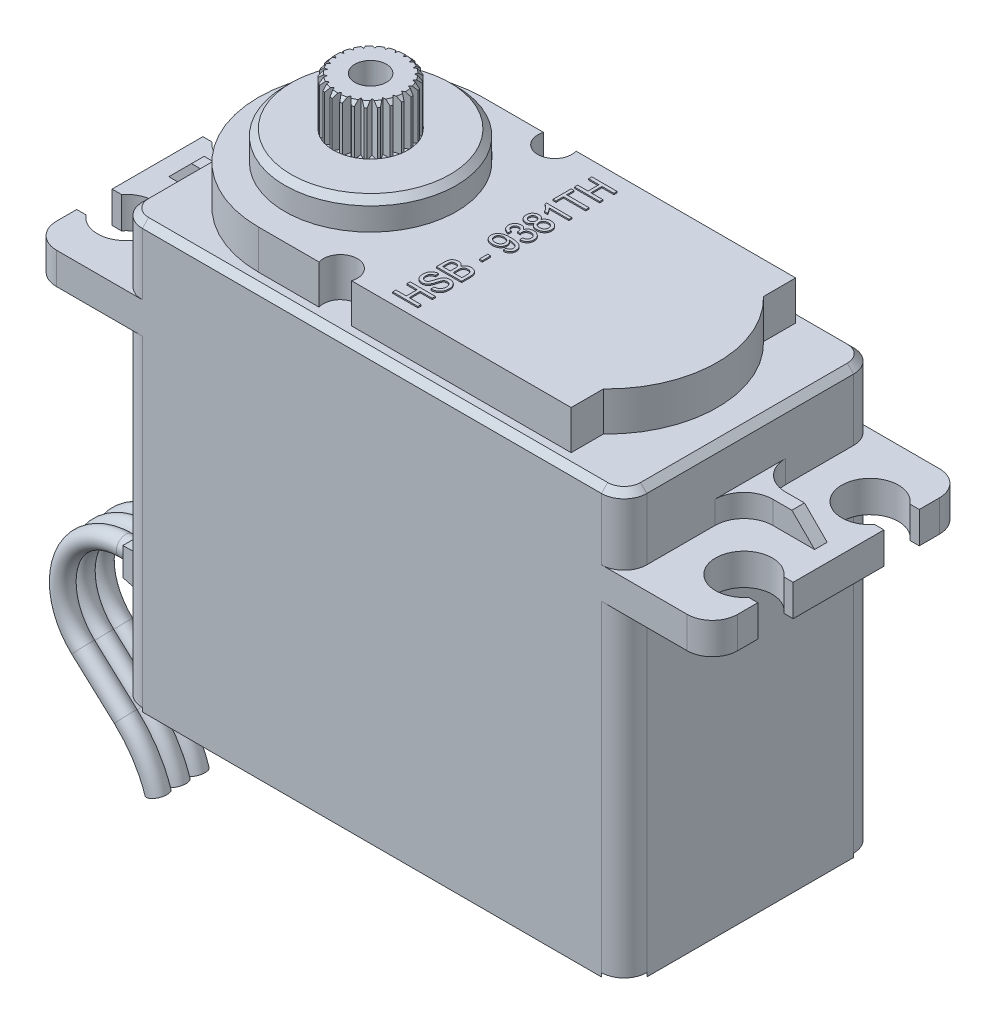
SolidWorks part; units mm, degrees
ref_plane "Ebene vorne" through (0, 0, 0) normal (0, 0, 1) x (1, 0, 0)
ref_plane "Ebene oben" through (0, 0, 0) normal (0, 1, 0) x (1, 0, 0)
ref_plane "Ebene rechts" through (0, 0, 0) normal (1, 0, 0) x (0, 0, -1)
sketch "Skizze1" plane through (0, 0, 0) normal (0, 0, 1) x (1, 0, 0)
  line L1 (-27, 27) -> (-20, 27)
  line L2 (-20, 27) -> (-20, 0)
  line L7 (-20, 0) -> (20, 0)
  line L8 (20, 0) -> (20, 27)
  line L9 (20, 27) -> (27, 27)
  line L10 (27, 27) -> (27, 29.5)
  line L11 (27, 29.5) -> (20, 29.5)
  line L12 (20, 29.5) -> (20, 34.9)
  line L14 (20, 34.9) -> (-20, 34.9)
  line L20 (-20, 34.9) -> (-20, 29.5)
  line L21 (-20, 29.5) -> (-27, 29.5)
  line L22 (-27, 29.5) -> (-27, 27)
  dimension "D1" = 40
  dimension "D2" = 27
  dimension "D6" = 54
  dimension "D7" = 2.5
  dimension "D11" = 5.4
extrude "Aufsatz-Linear austragen1" add sketch "Skizze1" along normal mid plane 20
sketch "Skizze2" plane through (0, 29.5, 0) normal (0, 1, 0) x (1, 0, 0)
  line L1 (24.5, -5) -> (-24.5, -5) construction
  line L2 (24.5, -5) -> (24.5, 5) construction
  line L3 (24.5, 5) -> (-24.5, 5) construction
  line L4 (-24.5, -5) -> (-24.5, 5) construction
  line L5 (24.5, -5) -> (-24.5, 5) construction
  line L6 (24.5, 5) -> (-24.5, -5) construction
  circle A0 centre (-24.5, 5) radius 2.25
  circle A1 centre (24.5, 5) radius 2.25
  circle A2 centre (24.5, -5) radius 2.25
  circle A3 centre (-24.5, -5) radius 2.25
  point P0 (0, 0)
  dimension "D1" = 4.5
  dimension "D2" = 10
  dimension "D3" = 49
extrude "Schnitt-Linear austragen1" cut sketch "Skizze2" against normal through all
sketch "Skizze6" plane through (0, 34.9, 0) normal (0, 1, 0) x (1, 0, 0)
  line L0 (-10.1, 8.9) -> (14.7, 8.9)
  line L1 (14.7, 8.9) -> (14.7, 6.35)
  line L2 (14.7, -6.35) -> (14.7, -8.9)
  line L3 (14.7, -8.9) -> (-10.1, -8.9)
  line L4 (-10.1, 0) -> (20, 0) construction
  line L5 (20, -10) -> (20, 10) construction
  line L6 (-20, -10) -> (-20, 10) construction
  line L8 (20, -10) -> (20, 10) construction
  arc A0 (-10.1, -8.9) -> (-10.1, 8.9) centre (-10.1, 0) cw
  arc A1 (14.7, 6.35) -> (14.7, -6.35) centre (8.5829, 0) cw
  circle A2 centre (24.5, 5) radius 2.25 construction
  point P13 (17.4, 0)
  point P17 (-19, 0)
  dimension "D1" = 17.8
  dimension "D2" = 34.7
  dimension "D3" = 12.7
  dimension "D4" = 2.6
  dimension "D5" = 34.6
extrude "Aufsatz-Linear austragen3" add sketch "Skizze6" along normal blind 3.1
sketch "Skizze7" plane through (0, 38, 0) normal (0, 1, 0) x (1, 0, 0)
  circle A0 centre (-10.1, 0) radius 6.8
  arc A1 (-10.1, 8.9) -> (-10.1, -8.9) centre (-10.1, 0) ccw construction
  dimension "D1" = 13.6
extrude "Aufsatz-Linear austragen4" add sketch "Skizze7" along normal blind 2.3
sketch "Skizze3" plane through (0, 40.3, 0) normal (0, 1, 0) x (1, 0, 0)
  circle A0 centre (-10.1, 0) radius 2.95
  circle A1 centre (-10.1, 0) radius 6.8 construction
  dimension "D1" = 5.9
extrude "Aufsatz-Linear austragen2" add sketch "Skizze3" along normal blind 3.8
fillet "Verrundung1" radius 2 4 edges at (27, 28.25, -10) (27, 28.25, 10) (-27, 28.25, -10) (-27, 28.25, 10)
sketch "Skizze4" plane through (0, 29.5, 0) normal (0, 1, 0) x (1, 0, 0)
  line L1 (-26.75, -5) -> (26.75, -5) construction
  line L2 (-25.75, 3.6) -> (-27.75, 3.6)
  line L3 (-25.75, 3.6) -> (-25.75, 6.4)
  line L4 (-25.75, 6.4) -> (-27.75, 6.4)
  line L5 (-27.75, 3.6) -> (-27.75, 6.4)
  line L6 (-25.75, 3.6) -> (-27.75, 6.4) construction
  line L7 (-25.75, 6.4) -> (-27.75, 3.6) construction
  line L8 (-25.75, -6.4) -> (-27.75, -6.4)
  line L9 (-25.75, -6.4) -> (-25.75, -3.6)
  line L10 (-25.75, -3.6) -> (-27.75, -3.6)
  line L11 (-27.75, -6.4) -> (-27.75, -3.6)
  line L12 (-25.75, -6.4) -> (-27.75, -3.6) construction
  line L13 (-25.75, -3.6) -> (-27.75, -6.4) construction
  line L14 (25.75, 6.4) -> (27.75, 6.4)
  line L15 (25.75, 6.4) -> (25.75, 3.6)
  line L16 (25.75, 3.6) -> (27.75, 3.6)
  line L17 (27.75, 6.4) -> (27.75, 3.6)
  line L18 (25.75, 6.4) -> (27.75, 3.6) construction
  line L19 (25.75, 3.6) -> (27.75, 6.4) construction
  line L20 (25.75, -3.6) -> (27.75, -3.6)
  line L21 (25.75, -3.6) -> (25.75, -6.4)
  line L22 (25.75, -6.4) -> (27.75, -6.4)
  line L23 (27.75, -3.6) -> (27.75, -6.4)
  line L24 (25.75, -3.6) -> (27.75, -6.4) construction
  line L25 (25.75, -6.4) -> (27.75, -3.6) construction
  line L26 (26.75, -5) -> (26.75, 5) construction
  line L27 (26.75, 5) -> (-26.75, 5) construction
  line L28 (-26.75, 5) -> (-26.75, -5) construction
  line L29 (-24.5, 5) -> (-26.75, 5) construction
  circle A0 centre (-24.5, 5) radius 2.25 construction
  circle A1 centre (-24.5, -5) radius 2.25 construction
  circle A2 centre (24.5, 5) radius 2.25 construction
  circle A3 centre (24.5, -5) radius 2.25 construction
  point P0 (-26.75, -5)
  point P2 (-26.75, 5)
  point P14 (26.75, 5)
  point P21 (26.75, -5)
  dimension "D1" = 2.8
  dimension "D2" = 2
extrude "Schnitt-Linear austragen2" cut sketch "Skizze4" against normal through all
chamfer "Fase1" distance 0.3 angle 45 1 edges at (-10.1, 44.1, 2.95)
sketch "Skizze5" plane through (0, 44.1, 0) normal (0, 1, 0) x (1, 0, 0)
  line L0 (-7.15, 0) -> (-10.1, 0) construction
  line L1 (-7.15, 0.2887) -> (-7.15, -0.2887)
  line L2 (-7.15, -0.2887) -> (-7.65, 0)
  line L3 (-7.65, 0) -> (-7.15, 0.2887)
  circle A0 centre (-10.1, 0) radius 2.95 construction
  circle A1 centre (-10.1, 0) radius 2.95 construction
  dimension "D1" = 0.5
extrude "Schnitt-Linear austragen3" cut sketch "Skizze5" against normal blind 3.9
pattern_circular "Kreismuster1" count 25 over 360 about axis through (-10.1, 44.1, 0) along (0, -1, 0) of "Schnitt-Linear austragen3" reverse direction yes
fillet "Verrundung2" radius 1.8 8 edges at (-20, 32.2, 10) (-20, 13.5, 10) (-20, 32.2, -10) (-20, 13.5, -10) (20, 13.5, 10) (20, 32.2, 10) (20, 32.2, -10) (20, 13.5, -10)
chamfer "Fase2" distance 1.2 angle 45 8 edges at (0, 0, 10) (-19.4728, 0, 9.4728) (19.4728, 0, 9.4728) (-20, 0, 0) (20, 0, 0) (-19.4728, 0, -9.4728) (19.4728, 0, -9.4728) (0, 0, -10)
hole_wizard "M3 Gewindebohrung1" positions "Skizze8" profile "Skizze9" tap size "M3" standard "DIN"
sketch "Skizze8" plane through (0, 44.1, 0) normal (0, 1, 0) x (1, 0, 0)
  point P0 (-10.1, 0)
sketch "Skizze9" plane through (-10.1, 44.1, 0) normal (1, 0, 0) x (0, 0, 1)
  line L0 (0, 0) -> (0, 9.2511)
  line L1 (0, 9.2511) -> (1.25, 8.5)
  line L2 (1.25, 8.5) -> (1.25, 0)
  line L5 (1.25, 0) -> (0, 0)
  line L10 (0, 9.2511) -> (-1.25, 8.5) construction
  line L11 (0, -6.35) -> (0, 107.95) construction
  dimension "Bohrerdurchmesser" = 2.5
  dimension "Bohrungstiefe" = 8.5
  dimension "Spitzenwinkel" = 118
cosmetic thread "Bohrungsgewinde1" parameters "D1"=6, "D2"=3
chamfer "Fase3" distance 0.5 angle 45 9 edges at (-10.1, 40.3, 6.8) (0, 34.9, -10) (19.4728, 34.9, -9.4728) (-19.4728, 34.9, -9.4728) (20, 34.9, 0) (-20, 34.9, 0) (19.4728, 34.9, 9.4728) (-19.4728, 34.9, 9.4728) (0, 34.9, 10)
sketch "Skizze10" plane through (0, 0, 0) normal (0, -1, 0) x (1, 0, 0)
  line L0 (-18.2, 10) -> (18.2, 10) construction
  line L1 (-20, 8.2) -> (-20, -8.2) construction
  line L3 (18.2, -8.2) -> (-18.2, -8.2) construction
  line L4 (18.2, -8.2) -> (18.2, 8.2) construction
  line L5 (18.2, 8.2) -> (-18.2, 8.2) construction
  line L6 (-18.2, -8.2) -> (-18.2, 8.2) construction
  line L7 (18.2, -8.2) -> (-18.2, 8.2) construction
  line L8 (18.2, 8.2) -> (-18.2, -8.2) construction
  circle A0 centre (-18.2, 8.2) radius 1.8
  circle A1 centre (18.2, 8.2) radius 1.8
  circle A2 centre (18.2, -8.2) radius 1.8
  circle A3 centre (-18.2, -8.2) radius 1.8
  point P12 (0, 0)
  dimension "D1" = 3.6
extrude "Schnitt-Linear austragen4" cut sketch "Skizze10" against normal blind 1.5 contours A3 | A0 | A1 | A2
sketch "Skizze11" plane through (0, 38, 0) normal (0, 1, 0) x (1, 0, 0)
  line L0 (-4, 8.5) -> (-4, -8.5) construction
  line L1 (-4, 0) -> (0, 0) construction
  line L2 (-20, -8.2) -> (-20, 8.2) construction
  circle A0 centre (-4, 8.5) radius 1.35
  circle A1 centre (-4, -8.5) radius 1.35
  dimension "D1" = 17
  dimension "D2" = 2.7
  dimension "D3" = 16
extrude "Schnitt-Linear austragen5" cut sketch "Skizze11" against normal up to surface (3.1 mm away) up to face at (0, 34.9, 0)
sketch "Skizze12" plane through (-20, 0, 0) normal (-1, 0, 0) x (0, 0, 1)
  line L0 (6.5029, 0) -> (-6.5029, 0) construction
  line L1 (3.5, 1.5) -> (-3.5, 1.5)
  line L2 (3.5, 1.5) -> (3.5, 5.5)
  line L3 (3.5, 5.5) -> (-3.5, 5.5)
  line L4 (-3.5, 1.5) -> (-3.5, 5.5)
  line L5 (3.5, 1.5) -> (-3.5, 5.5) construction
  line L6 (3.5, 5.5) -> (-3.5, 1.5) construction
  line L7 (0, 0) -> (0, 3.5) construction
  point P0 (0, 3.5)
  dimension "D1" = 4
  dimension "D2" = 7
  dimension "D3" = 3.5
ref_plane "Ebene1" through (-27, 0, 0) normal (-1, 0, 0) x (0, 0, 1)
sketch "Skizze13" plane through (-27, 0, 0) normal (-1, 0, 0) x (0, 0, 1)
  line L1 (2.75, 2.4) -> (-2.75, 2.4)
  line L2 (2.75, 2.4) -> (2.75, 4.6)
  line L3 (2.75, 4.6) -> (-2.75, 4.6)
  line L4 (-2.75, 2.4) -> (-2.75, 4.6)
  line L5 (2.75, 2.4) -> (-2.75, 4.6) construction
  line L6 (2.75, 4.6) -> (-2.75, 2.4) construction
  point P0 (0, 3.5)
  dimension "D1" = 2.2
  dimension "D2" = 5.5
loft "Ausformung1" add profiles "Skizze13", "Skizze12" connector at (-27, 4.6, -2.75) connector at (-20, 5.5, -3.5)
sketch "Skizze15" plane through (-27, 0, 0) normal (-1, 0, 0) x (0, 0, 1)
  line L0 (-1.51, 3.5) -> (0, 3.5) construction
  line L1 (0, 3.5) -> (1.51, 3.5) construction
  circle A0 centre (0, 3.5) radius 0.75
  circle A1 centre (-1.51, 3.5) radius 0.75
  circle A2 centre (1.51, 3.5) radius 0.75
  dimension "D1" = 1.5
  dimension "D2" = 1.51
sketch "Skizze16" plane through (0, 0, 0) normal (0, 0, 1) x (1, 0, 0)
  line L0 (-27, 3.5) -> (-28, 3.5)
  line L1 (-27, 4.25) -> (-27, 2.75) construction
  line L2 (-31.3702, -5.1935) -> (-28, -8.2686)
  arc A0 (-28, 3.5) -> (-31.3702, -5.1935) centre (-28, -1.5) ccw
  arc A1 (-28, -8.2686) -> (-25.4374, -12.2225) centre (-34.2689, -15.139) cw
  dimension "D1" = 1
  dimension "D2" = 5
sweep "Austragung1" add profiles "Skizze15" path "Skizze16"
sketch "Skizze17" plane through (0, 38, 0) normal (0, 1, 0) x (1, 0, 0)
  line L0 (1.7845, -8.3394) -> (1.7845, 8.9) construction
  line L2 (14.7, 8.9) -> (-2.7106, 8.9) construction
  text T0 "HSB - 9381TH" font "Arial" height 2
extrude "Aufsatz-Linear austragen5" add sketch "Skizze17" along normal blind 0.1
sketch "Skizze18" plane through (0, 29.5, 0) normal (0, 1, 0) x (1, 0, 0)
  line L0 (-25.6, 0.5) -> (-25.6, -0.5)
  line L1 (-25.6, -0.5) -> (-22.3, -0.5)
  line L2 (-20, -8.2) -> (-20, 8.2) construction
  line L3 (-20, -2.8) -> (-20, 2.8)
  line L4 (-25.6, 0.5) -> (-22.3, 0.5)
  line L5 (-25.6, 0) -> (-20, 0) construction
  line L6 (-20, -8.2) -> (-20, 8.2) construction
  line L7 (-25.6, 0) -> (-27, 0) construction
  line L8 (-27, -3.6) -> (-27, 3.6) construction
  arc A0 (-22.3, -0.5) -> (-20, -2.8) centre (-22.3, -2.8) cw
  arc A1 (-22.3, 0.5) -> (-20, 2.8) centre (-22.3, 2.8) ccw
  dimension "D1" = 5.6
  dimension "D2" = 1
  dimension "D3" = 5.6
extrude "Aufsatz-Linear austragen6" add sketch "Skizze18" along normal blind 1.8
chamfer "Fase4" distance 1.8 angle 45 1 edges at (-25.6, 31.3, 0)
mirror "Spiegeln1" about plane through (0, 0, 0) normal (1, 0, 0) of "Fase4", "Aufsatz-Linear austragen6"
